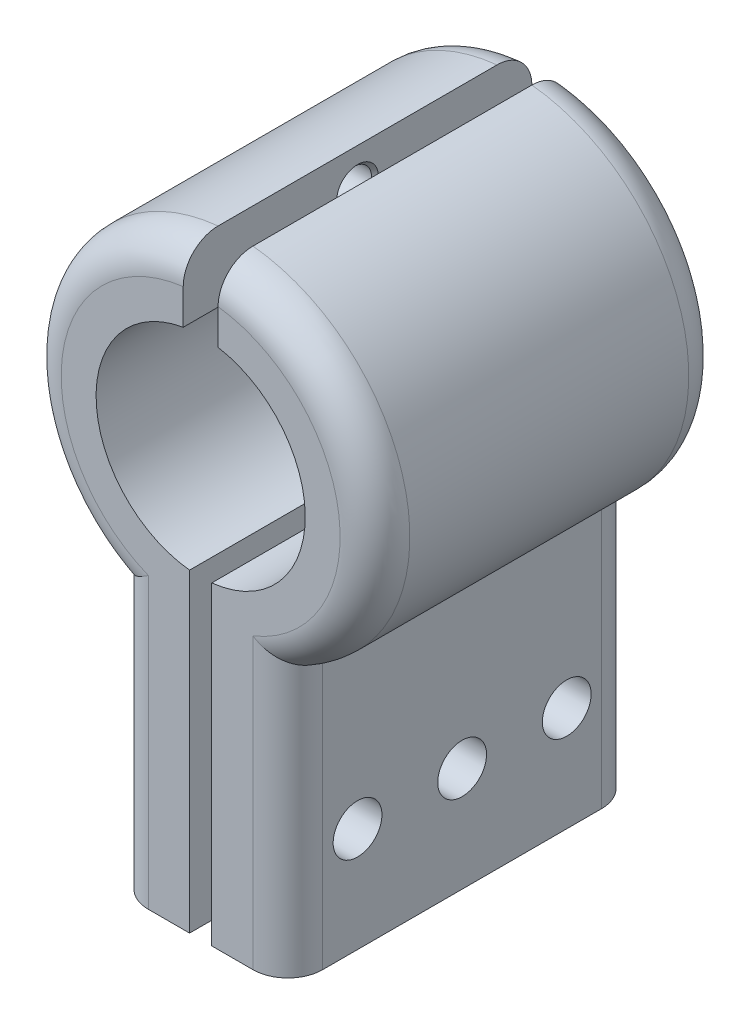
SolidWorks part; units mm, degrees
ref_plane "Front Plane" through (0, 0, 0) normal (0, 0, 1) x (1, 0, 0)
ref_plane "Top Plane" through (0, 0, 0) normal (0, 1, 0) x (1, 0, 0)
ref_plane "Right Plane" through (0, 0, 0) normal (1, 0, 0) x (0, 0, -1)
sketch "Sketch1" plane through (0, 0, 0) normal (0, 0, 1) x (1, 0, 0)
  line L0 (0, -60) -> (0, 0) construction
  line L2 (-12.5, -21.6506) -> (-12.5, -60)
  line L3 (-12.5, -60) -> (-1.59, -60)
  line L4 (12.5, -21.6506) -> (12.5, -60)
  line L5 (-2.5, 14.7902) -> (2.5, 14.7902) construction
  line L7 (-2.5, 24.8747) -> (-2.5, 14.7902)
  line L9 (2.5, 24.8747) -> (2.5, 14.7902)
  line L10 (0, 14.7902) -> (0, 0) construction
  line L11 (-1.59, -14.9155) -> (-1.59, -60)
  line L12 (1.59, -60) -> (1.59, -14.9155)
  line L13 (1.59, -60) -> (12.5, -60)
  line L14 (-1.59, -60) -> (1.59, -60) construction
  arc A0 (-2.5, 14.7902) -> (-1.59, -14.9155) centre (0, 0) ccw
  arc A1 (12.5, -21.6506) -> (2.5, 24.8747) centre (0, 0) ccw
  arc A2 (-2.5, 24.8747) -> (-12.5, -21.6506) centre (0, 0) ccw
  arc A3 (1.59, -14.9155) -> (2.5, 14.7902) centre (0, 0) ccw
  dimension "D1" = 30
  dimension "D2" = 25
  dimension "D3" = 5
  dimension "D4" = 25
  dimension "D5" = 3.18
  dimension "D6" = 60
extrude "Boss-Extrude1" add sketch "Sketch1" along normal mid plane 50
fillet "Fillet1" radius 5 4 edges at (-24.4418, 5.2534, 25) (-24.4418, 5.2534, -25) (-12.5, -40.8253, 25) (-12.5, -40.8253, -25)
fillet "Fillet2" radius 5 4 edges at (24.4418, 5.2534, -25) (12.5, -40.8253, -25) (12.5, -40.8253, 25) (24.4418, 5.2534, 25)
sketch "Sketch3" plane through (-12.5, 0, 0) normal (-1, 0, 0) x (0, 0, 1)
  line L0 (0, 0) -> (0, -45) construction
  line L1 (-15, -45) -> (15, -45) construction
  circle A0 centre (0, -45) radius 3.5
  circle A1 centre (-15, -45) radius 3.5
  circle A2 centre (15, -45) radius 3.5
  point P6 (0, -45)
  dimension "D1" = 7
  dimension "D3" = 30
  dimension "D2" = 45
extrude "Cut-Extrude1" cut sketch "Sketch3" against normal through all both and the other way through all
sketch "Sketch4" plane through (0, 0, 0) normal (1, 0, 0) x (0, 0, -1)
  line L0 (0, 19.5) -> (0, 0) construction
  circle A0 centre (0, 19.5) radius 2.5
  dimension "D1" = 19.5
  dimension "D2" = 5
extrude "Cut-Extrude2" cut sketch "Sketch4" against normal mid plane 16
chamfer "Chamfer1" distance 0.5 angle 45 2 edges at (-2.5, 17, 0) (-8, 19.5, -2.5)
chamfer "Chamfer2" distance 0.5 angle 45 2 edges at (8, 19.5, -2.5) (2.5, 22, 0)
